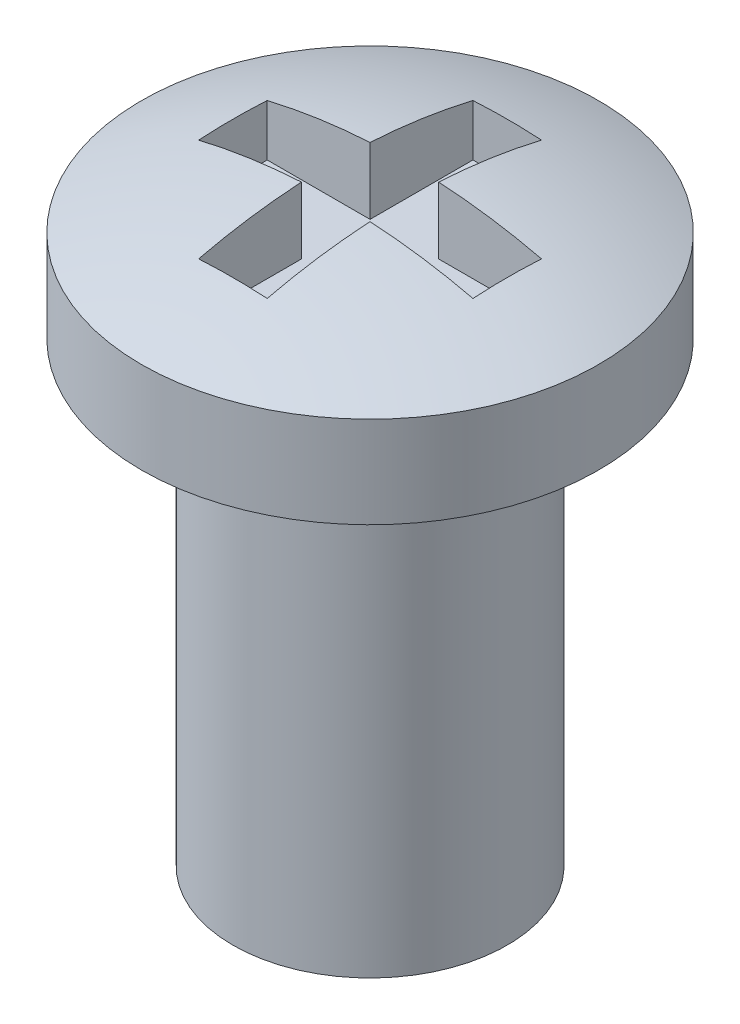
SolidWorks part; units mm, degrees
material "1023 Carbon Steel Sheet (SS)"
ref_plane "Front Plane" through (0, 0, 0) normal (0, 0, 1) x (1, 0, 0)
ref_plane "Top Plane" through (0, 0, 0) normal (0, 1, 0) x (1, 0, 0)
ref_plane "Right Plane" through (0, 0, 0) normal (1, 0, 0) x (0, 0, -1)
ref_plane "Top Plane1" through (0, 6.5, 0) normal (0, 1, 0) x (1, 0, 0)
sketch "Sketch1" plane through (0, 0, 0) normal (0, 1, 0) x (1, 0, 0)
  circle A0 centre (0, 0) radius 1.5
  dimension "D1" = 3
extrude "Boss-Extrude1" add sketch "Sketch1" along normal blind 5
sketch "Sketch2" plane through (0, 5, 0) normal (0, 1, 0) x (1, 0, 0)
  circle A0 centre (0, 0) radius 2.5
  dimension "D1" = 5
extrude "Boss-Extrude2" add sketch "Sketch2" along normal blind 1
dome "Dome1" faces to dome 1 distance 0.5 reverse direction no elliptical dome no face at (0, 6, 2.5) parameters "D1"=0.5
sketch "Sketch3" plane through (0, 6.5, 0) normal (0, 1, 0) x (1, 0, 0)
  line L0 (-2.5, 0) -> (2.5, 0) construction
  line L1 (0, 2.5) -> (0, -2.5) construction
  line L2 (-1.5, 0.375) -> (1.5, -0.375) construction
  line L3 (-1.5, 0.375) -> (1.5, 0.375)
  line L4 (-1.5, 0.375) -> (-1.5, -0.375)
  line L5 (-1.5, -0.375) -> (1.5, -0.375)
  line L6 (1.5, 0.375) -> (1.5, -0.375)
  line L7 (0.375, 1.5) -> (-0.375, -1.5) construction
  line L8 (-0.375, 1.5) -> (0.375, 1.5)
  line L9 (-0.375, 1.5) -> (-0.375, -1.5)
  line L10 (-0.375, -1.5) -> (0.375, -1.5)
  line L11 (0.375, 1.5) -> (0.375, -1.5)
  circle A0 centre (0, 0) radius 2.5 construction
  dimension "D1" = 1.5
  dimension "D2" = 1.5
  dimension "D3" = 0.75
  dimension "D4" = 0.75
extrude "Cut-Extrude1" cut sketch "Sketch3" against normal blind 0.75 contours L9 L3 L4 L5 | L11 L3 L9 L5 | L11 L8 L9 L3 | L3 L11 L5 L6 | L11 L5 L9 L10 region at (-0.9375, 6.5, 0) region at (0, 6.5, -0.9375) region at (0, 6.5, 0) region at (0.9375, 6.5, 0) region at (0, 6.5, 0.9375)
